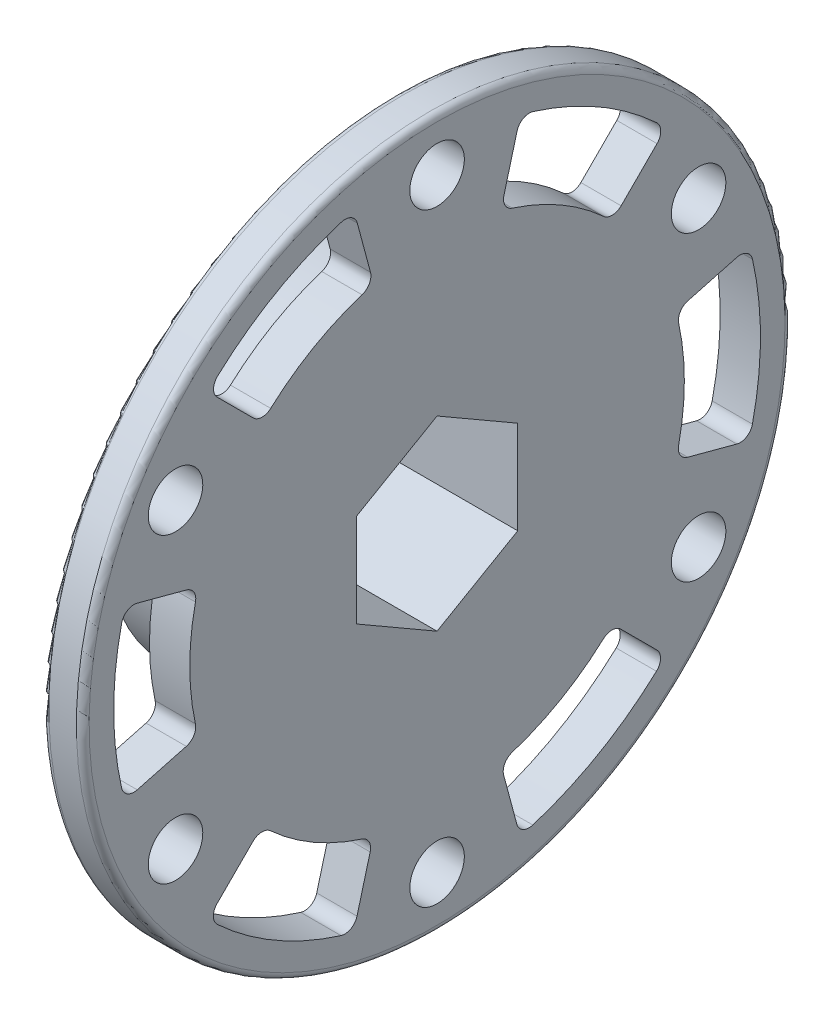
SolidWorks part; units mm, degrees
ref_plane "Front Plane" through (0, 0, 0) normal (0, 0, 1) x (1, 0, 0)
ref_plane "Top Plane" through (0, 0, 0) normal (0, 1, 0) x (1, 0, 0)
ref_plane "Right Plane" through (0, 0, 0) normal (1, 0, 0) x (0, 0, -1)
ref_plane "Plane1" through (9.525, 0, 0) normal (-1, 0, 0) x (0, -1, 0)
sketch "Sketch1" plane through (9.525, 0, 0) normal (-1, 0, 0) x (0, -1, 0)
  circle A0 centre (0, 0) radius 27.94
extrude "Boss-Extrude1" add sketch "Sketch1" against normal blind 3.175
sketch "Sketch2" plane through (9.525, 0, 0) normal (-1, 0, 0) x (0, 0, 1)
  line L0 (-24.6179, -6.6489) -> (-18.8223, -5.096)
  line L1 (-18.829, 5.0715) -> (-24.6245, 6.6244)
  arc A0 (-18.8223, -5.096) -> (-18.829, 5.0715) centre (0, 0) cw
  arc A1 (-24.6245, 6.6244) -> (-24.6179, -6.6489) centre (0, 0) ccw
extrude "Cut-Extrude1" cut sketch "Sketch2" against normal through all
sketch3d "3DSketch1"
  point P0 (111.1125, 0, 0)
  point P1 (11.1125, 0, 0)
ref_axis "Axis1" through (111.1125, 0, 0) along (-1, 0, 0)
pattern_circular "CirPattern1" count 6 over 360 about axis through (111.1125, 0, 0) along (-1, 0, 0) of "Cut-Extrude1"
sketch "Sketch3" plane through (9.525, 0, 0) normal (-1, 0, 0) x (0, 0, 1)
  circle A0 centre (-20.6222, 11.9063) radius 2.15
extrude "Cut-Extrude2" cut sketch "Sketch3" against normal through all
sketch3d "3DSketch2"
  point P0 (111.1125, 0, 0)
  point P1 (11.1125, 0, 0)
ref_axis "Axis2" through (111.1125, 0, 0) along (-1, 0, 0)
pattern_circular "CirPattern2" count 6 over 360 about axis through (111.1125, 0, 0) along (-1, 0, 0) of "Cut-Extrude2"
sketch "Sketch4" plane through (9.525, 0, 0) normal (-1, 0, 0) x (0, 0, 1)
  circle A0 centre (0, 0) radius 14.2949
extrude "Boss-Extrude2" add sketch "Sketch4" along normal blind 9.525
sketch "Sketch5" plane through (0, 0, 0) normal (-1, 0, 0) x (0, 0, 1)
  line L0 (-6.3627, -3.6735) -> (0, -7.347)
  line L1 (0, -7.347) -> (6.3627, -3.6735)
  line L2 (6.3627, -3.6735) -> (6.3627, 3.6735)
  line L3 (6.3627, 3.6735) -> (0, 7.347)
  line L4 (0, 7.347) -> (-6.3627, 3.6735)
  line L5 (-6.3627, 3.6735) -> (-6.3627, -3.6735)
extrude "Cut-Extrude3" cut sketch "Sketch5" against normal through all
chamfer "Chamfer1" distance 1 angle 45 1 edges at (0, -14.2949, 0)
fillet "Fillet1" radius 0.5 2 edges at (12.7, 27.94, 0) (9.525, 27.94, 0) tangent propagation no
fillet "Fillet2" radius 1 24 edges at (11.1125, 18.8421, -5.0224) (11.1125, -6.6244, 24.6245) (11.1125, 18.8486, 4.9979) (11.1125, -5.0715, 18.829) (11.1125, 24.6442, 6.5508) (11.1125, -5.096, -18.8223) (11.1125, 24.6377, -6.5753) (11.1125, 17.9953, -18.0671) (11.1125, 6.6244, -24.6245) (11.1125, -24.6377, 6.5753) (11.1125, 6.6489, 24.6179) (11.1125, 5.096, 18.8223) (11.1125, -13.7526, 13.8245) (11.1125, 5.0715, -18.829) (11.1125, -13.7706, -13.8065) (11.1125, -6.6489, -24.6179) (11.1125, -18.8486, -4.9979) (11.1125, 13.7526, -13.8245) (11.1125, -24.6442, -6.5508) (11.1125, 13.7706, 13.8065) (11.1125, -18.0133, -18.0492) (11.1125, 18.0133, 18.0492) (11.1125, -17.9953, 18.0671) (11.1125, -18.8421, 5.0224) tangent propagation no
fillet "Fillet3" radius 1.27 1 edges at (9.525, 14.2949, 0) tangent propagation no
